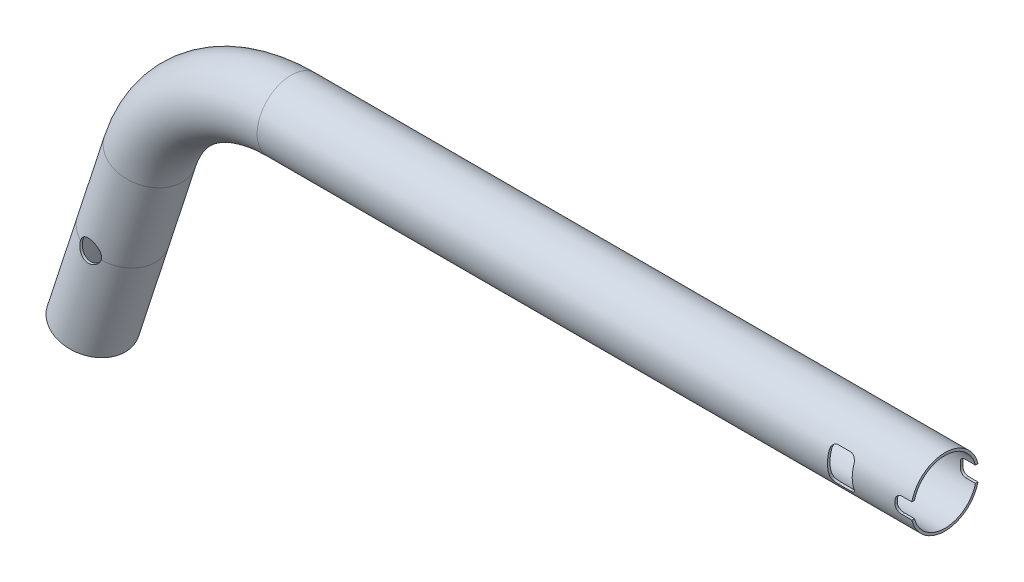
SolidWorks part; units mm, degrees
ref_plane "Front Plane" through (0, 0, 0) normal (0, 0, 1) x (1, 0, 0)
ref_plane "Top Plane" through (0, 0, 0) normal (0, 1, 0) x (1, 0, 0)
ref_plane "Right Plane" through (0, 0, 0) normal (1, 0, 0) x (0, 0, -1)
sketch "Sketch1" plane through (0, 0, 0) normal (0, 0, 1) x (1, 0, 0)
  line L0 (-94.2504, 0) -> (94.2504, 0)
  line L1 (-139.9011, -33.1672) -> (-148.6196, -60)
  line L2 (94.2504, 0) -> (117.2504, 0)
  line L3 (-148.6196, -60) -> (-158.3672, -90)
  arc A0 (-94.2504, 0) -> (-139.9011, -33.1672) centre (-94.2504, -48) ccw
  point P4 (0, 0)
  point P10 (-148.6196, -60)
  dimension "D2" = 48
  dimension "D7" = 90
  dimension "D1" = 72
  dimension "D3" = 60
  dimension "D4" = 242.87
  dimension "D5" = 23
  dimension "D6" = 72
ref_plane "Plane1" through (94.2504, 0, 0) normal (1, 0, 0) x (0, 0, -1)
sketch "Sketch3" plane through (94.2504, 0, 0) normal (1, 0, 0) x (0, 0, -1)
  circle A0 centre (0, 0) radius 11
  circle A1 centre (0, 0) radius 10.2
  dimension "D1" = 0.8
  dimension "D2" = 22
sweep "Sweep2" add profiles "Sketch3" path "Sketch1"
ref_axis "Axis1" through (117.2504, 0, 0) along (-1, 0, 0)
ref_axis "Axis2" through (-137.9031, -27.018, 0) along (-0.309, -0.9511, 0)
sketch "Sketch4" plane through (0, 0, 0) normal (0, 0, 1) x (1, 0, 0)
  line L0 (-159.0812, -56.6008) -> (-138.158, -63.3992) construction
  line L1 (94.2504, -101.4635) -> (94.2504, 101.4635) construction
  line L2 (117.2504, 0) -> (94.2504, 0) construction
  line L3 (117.2504, -11) -> (117.2504, 11) construction
  line L4 (117.2504, 0) -> (-94.2504, 0) construction
  line L6 (92.2504, -5.5) -> (96.2504, -5.5)
  line L7 (90.2504, -3.5) -> (90.2504, 3.5)
  line L8 (92.2504, 5.5) -> (96.2504, 5.5)
  line L9 (98.2504, -3.5) -> (98.2504, 3.5)
  line L10 (90.2504, -5.5) -> (98.2504, 5.5) construction
  line L11 (90.2504, 5.5) -> (98.2504, -5.5) construction
  circle A0 centre (-148.6196, -60) radius 3.5
  arc A1 (92.2504, -5.5) -> (90.2504, -3.5) centre (92.2504, -3.5) cw
  arc A2 (98.2504, -3.5) -> (96.2504, -5.5) centre (96.2504, -3.5) cw
  arc A3 (96.2504, 5.5) -> (98.2504, 3.5) centre (96.2504, 3.5) cw
  arc A4 (92.2504, 5.5) -> (90.2504, 3.5) centre (92.2504, 3.5) ccw
  dimension "D1" = 23
  dimension "D4" = 2
  dimension "D6" = 7
  dimension "D2" = 8
  dimension "D3" = 11
extrude "Cut-Extrude1" cut sketch "Sketch4" along normal up to next
sketch "Sketch5" plane through (0, 0, 0) normal (0, 0, 1) x (1, 0, 0)
  line L0 (-158.3204, -56.848) -> (-138.9188, -63.152) construction
  circle A0 centre (-148.6196, -60) radius 3.3
extrude "Cut-Extrude2" cut sketch "Sketch5" against normal through all
sketch "Sketch6" plane through (0, 0, 0) normal (0, 0, 1) x (1, 0, 0)
  line L4 (117.3242, 2.5547) -> (117.2504, -2.5547)
  line L5 (117.2504, -11) -> (117.2504, 11) construction
  line L6 (117.2504, -2.5547) -> (114.0504, -2.5547)
  line L7 (112.0504, -0.5547) -> (112.0504, 0.5547)
  line L8 (114.0504, 2.5547) -> (117.3242, 2.5547)
  arc A2 (114.0504, -2.5547) -> (112.0504, -0.5547) centre (114.0504, -0.5547) cw
  arc A3 (114.0504, 2.5547) -> (112.0504, 0.5547) centre (114.0504, 0.5547) ccw
  point P7 (117.2873, 0)
  point P11 (112.0504, -2.5547)
  dimension "D1" = 5.11
  dimension "D3" = 2
  dimension "D2" = 5.2
extrude "Cut-Extrude3" cut sketch "Sketch6" against normal through all and the other way through all
